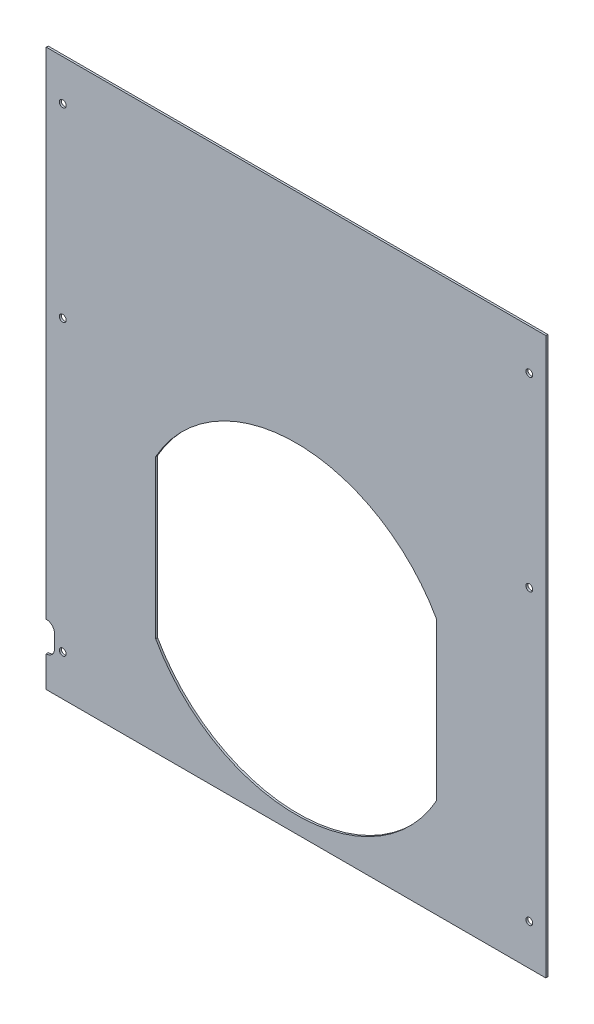
SolidWorks part; units mm, degrees
material "Low Carbon Steel"
ref_plane "Front Plane" through (0, 0, 0) normal (0, 0, 1) x (1, 0, 0)
ref_plane "Top Plane" through (0, 0, 0) normal (0, 1, 0) x (1, 0, 0)
ref_plane "Right Plane" through (0, 0, 0) normal (1, 0, 0) x (0, 0, -1)
sketch "Sketch1" plane through (0, 0, 0) normal (0, 0, 1) x (1, 0, 0)
  line L0 (-240, -267.5) -> (240, 267.5) construction
  line L1 (-240, 267.5) -> (240, 267.5) construction
  line L2 (-240, 267.5) -> (-240, -267.5) construction
  line L3 (-240, -267.5) -> (240, -267.5) construction
  line L4 (240, 267.5) -> (240, -267.5) construction
  line L5 (240, 267.5) -> (240.2436, 266.1724) construction
  line L6 (-242, 269.5) -> (242, 269.5)
  line L7 (242, 269.5) -> (242, -269.5)
  line L8 (-242, -269.5) -> (242, -269.5)
  line L9 (-242, 269.5) -> (-242, -269.5)
  line L10 (0, -97.5) -> (0, 0) construction
  line L11 (136, -21.0801) -> (136, -173.9199)
  line L12 (-136, -21.0801) -> (-136, -173.9199)
  arc A0 (136, -21.0801) -> (-136, -21.0801) centre (0, -97.5) ccw
  arc A1 (-136, -173.9199) -> (136, -173.9199) centre (0, -97.5) ccw
  dimension "D4" = 312
  dimension "D1" = 480
  dimension "D2" = 535
  dimension "D3" = 2
  dimension "D5" = 170
  dimension "D6" = 272
base flange "Base-Flange1" sketch "Sketch1" thickness 1.8974 reverse thickness direction no parameters "D1"=3.175
hole_wizard "M6 Clearance Hole1" positions "Sketch20" profile "Sketch19" hole size "M6" standard "Peddi DIN" end condition through all
sketch "Sketch20" plane through (0, 0, -1.8974) normal (0, 0, -1) x (-1, 0, 0)
  line L2 (-226, 230) -> (226, 230) construction
  line L4 (226, 230) -> (226, 50) construction
  line L7 (226, 50) -> (226, -230) construction
  line L9 (-226, 230) -> (-226, 50) construction
  line L10 (-226, 50) -> (-226, -230) construction
  line L11 (0, 0) -> (0, 230) construction
  arc A1 (136, -21.0801) -> (-136, -21.0801) centre (0, -97.5) ccw construction
  point P0 (-226, 230)
  point P4 (226, 230)
  point P6 (226, -230)
  point P8 (-226, -230)
  point P10 (-226, 50)
  point P12 (226, 50)
  dimension "D1" = 132.5
  dimension "D2" = 280
  dimension "D3" = 452
  dimension "D4" = 180
sketch "Sketch19" plane through (226, 230, -1.8974) normal (1, 0, 0) x (0, 1, 0)
  line L0 (0, 0) -> (0, 1.8974)
  line L1 (0, 1.8974) -> (3.3, 1.8974)
  line L2 (3.3, 1.8974) -> (3.3, 0)
  line L5 (3.3, 0) -> (0, 0)
  line L11 (0, -6.35) -> (0, 107.95) construction
  dimension "Thru Hole Dia." = 6.6
  dimension "Thru Hole Depth" = 1.8974
sketch "Sketch21" plane through (0, 0, 0) normal (0, 0, 1) x (1, 0, 0)
  line L2 (-234, -218.5) -> (-234, -231.5)
  line L4 (-234, -225) -> (-242, -225) construction
  line L6 (-242, 269.5) -> (-242, -269.5) construction
  line L7 (-242, -210.5) -> (-242, -239.5)
  line L8 (-242, -269.5) -> (242, -269.5) construction
  arc A0 (-234, -231.5) -> (-242, -239.5) centre (-242, -231.5) cw
  arc A1 (-242, -210.5) -> (-234, -218.5) centre (-242, -218.5) cw
  dimension "D4" = 8
  dimension "D1" = 29
  dimension "D2" = 30
  dimension "D3" = 8
extrude "Cut-Extrude1" cut sketch "Sketch21" against normal through all and the other way through all
other "Freeze***"
sketch "Bend-Lines1" [suppressed] plane through (0, 0, 0) normal (0, 1, 0) x (1, 0, 0)
sketch "Bounding-Box1" [suppressed] plane through (0, 0, 0) normal (0, 1, 0) x (1, 0, 0)
sheet metal parameters "Sheet-Metal16" thickness 1.8974 parameters "D1"=3.175
flat pattern "Flat-Pattern16" [suppressed]
sketch "Bend-Lines2" plane through (0, 0, 0) normal (0, 1, 0) x (1, 0, 0)
sketch "Bounding-Box2" [suppressed] plane through (0, 0, 0) normal (0, 1, 0) x (1, 0, 0)
sheet metal parameters "Sheet-Metal19" thickness 1.8974 parameters "D1"=3.175
flat pattern "Flat-Pattern16"
sketch "Bend-Lines2" plane through (0, 0, 0) normal (0, 1, 0) x (1, 0, 0)
sketch3d "Bounding-Box2" [suppressed]
  line L0 (242, 269.5, 0) -> (242, -269.5, 0) construction
  line L1 (-242, 269.5, 0) -> (-242, -269.5, 0) construction
  line L2 (242, 269.5, 0) -> (-242, 269.5, 0) construction
  line L3 (242, -269.5, 0) -> (-242, -269.5, 0) construction
sheet metal parameters "Sheet-Metal21" thickness 1.8974 parameters "D1"=3.175
flat pattern "Flat-Pattern16"
sketch "Bend-Lines2" plane through (0, 0, 0) normal (0, 1, 0) x (1, 0, 0)
sketch3d "Bounding-Box2" [suppressed]
  line L0 (242, 269.5, 0) -> (242, -269.5, 0) construction
  line L1 (-242, 269.5, 0) -> (-242, -269.5, 0) construction
  line L2 (242, 269.5, 0) -> (-242, 269.5, 0) construction
  line L3 (242, -269.5, 0) -> (-242, -269.5, 0) construction
